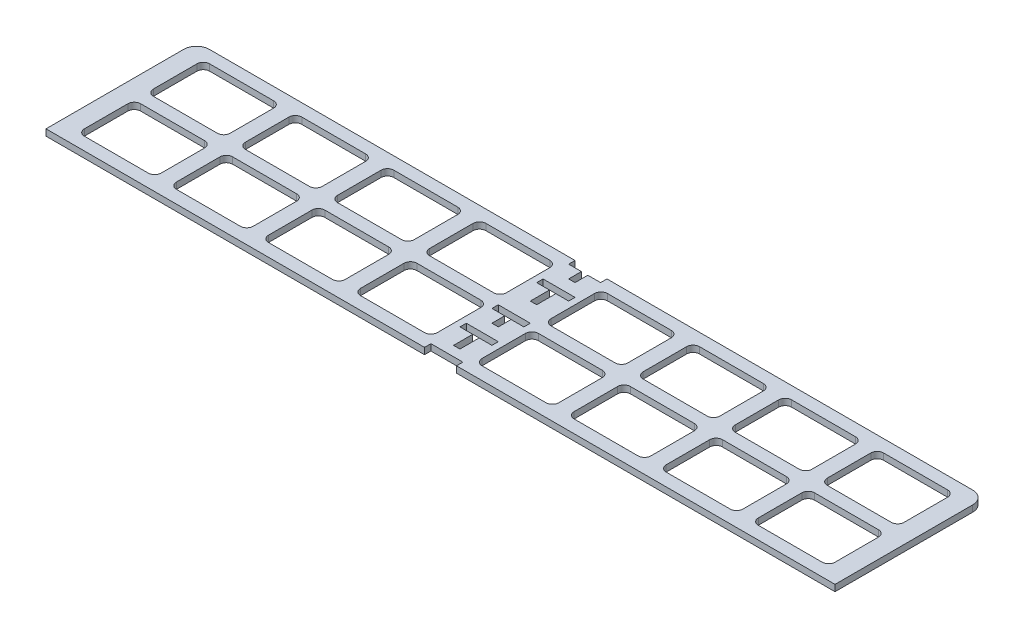
SolidWorks part; units mm, degrees
material "Balsa"
ref_plane "Front Plane" through (0, 0, 0) normal (0, 0, 1) x (1, 0, 0)
ref_plane "Top Plane" through (0, 0, 0) normal (0, 1, 0) x (1, 0, 0)
ref_plane "Right Plane" through (0, 0, 0) normal (1, 0, 0) x (0, 0, -1)
sketch "Sketch1" plane through (0, 0, 0) normal (0, 1, 0) x (1, 0, 0)
  line L0 (0, 0) -> (388.62, 0)
  line L1 (375.92, 149.479) -> (0, 149.479)
  line L3 (388.62, 0) -> (388.62, 136.779)
  line L4 (0, 149.479) -> (0, 130.429)
  line L5 (0, 130.429) -> (-3.175, 130.429)
  line L6 (-3.175, 130.429) -> (-3.175, 111.379)
  line L7 (-3.175, 111.379) -> (0, 111.379)
  line L8 (0, 111.379) -> (0, 92.329)
  line L9 (0, 92.329) -> (-3.175, 92.329)
  line L10 (-3.175, 92.329) -> (-3.175, 73.279)
  line L11 (-3.175, 73.279) -> (0, 73.279)
  line L12 (0, 73.279) -> (0, 54.229)
  line L13 (0, 54.229) -> (-3.175, 54.229)
  line L14 (-3.175, 54.229) -> (-3.175, 35.179)
  line L15 (-3.175, 35.179) -> (0, 35.179)
  line L16 (0, 35.179) -> (0, 16.129)
  line L17 (0, 16.129) -> (-3.175, 16.129)
  line L23 (-3.175, 0) -> (0, 0)
  line L24 (-3.175, 16.129) -> (-3.175, 0)
  arc A0 (375.92, 149.479) -> (388.62, 136.779) centre (375.92, 136.779) cw
  point P7 (388.62, 149.479)
  dimension "D4" = 12.7
  dimension "D22" = 136.779
  dimension "D2" = 388.62
  dimension "D3" = 149.479
  dimension "D5" = 19.05
  dimension "D6" = 19.05
  dimension "D7" = 3.175
  dimension "D8" = 19.05
  dimension "D9" = 19.05
  dimension "D10" = 19.05
  dimension "D11" = 19.05
  dimension "D12" = 19.05
  dimension "D15" = 3.175
  dimension "D16" = 3.175
  dimension "D17" = 3.175
  dimension "D18" = 375.92
  dimension "D19" = 3.175
  dimension "D23" = 3.175
extrude "Boss-Extrude1" add sketch "Sketch1" along normal blind 6.35
sketch "Sketch2" plane through (0, 6.35, 0) normal (0, 1, 0) x (1, 0, 0)
  line L0 (110.49, 19.05) -> (110.49, 62.23)
  line L9 (116.84, 12.7) -> (180.34, 12.7)
  line L82 (186.69, 19.05) -> (186.69, 62.23)
  line L83 (116.84, 68.58) -> (180.34, 68.58)
  line L84 (201.93, 19.05) -> (201.93, 62.23)
  line L85 (208.28, 12.7) -> (271.78, 12.7)
  line L86 (278.13, 19.05) -> (278.13, 62.23)
  line L87 (208.28, 68.58) -> (271.78, 68.58)
  line L88 (293.37, 19.05) -> (293.37, 62.23)
  line L89 (299.72, 12.7) -> (363.22, 12.7)
  line L90 (369.57, 19.05) -> (369.57, 62.23)
  line L91 (25.4, 12.7) -> (88.9, 12.7)
  line L92 (19.05, 19.05) -> (19.05, 62.23)
  line L93 (25.4, 68.58) -> (88.9, 68.58)
  line L94 (95.25, 19.05) -> (95.25, 62.23)
  line L95 (299.72, 68.58) -> (363.22, 68.58)
  line L96 (110.49, 87.63) -> (110.49, 130.81)
  line L97 (116.84, 81.28) -> (180.34, 81.28)
  line L98 (186.69, 87.63) -> (186.69, 130.81)
  line L99 (116.84, 137.16) -> (180.34, 137.16)
  line L100 (201.93, 87.63) -> (201.93, 130.81)
  line L101 (208.28, 81.28) -> (271.78, 81.28)
  line L102 (278.13, 87.63) -> (278.13, 130.81)
  line L103 (208.28, 137.16) -> (271.78, 137.16)
  line L104 (293.37, 87.63) -> (293.37, 130.81)
  line L105 (299.72, 81.28) -> (363.22, 81.28)
  line L106 (369.57, 87.63) -> (369.57, 130.81)
  line L107 (299.72, 137.16) -> (363.22, 137.16)
  line L108 (19.05, 87.63) -> (19.05, 130.81)
  line L109 (25.4, 81.28) -> (88.9, 81.28)
  line L110 (95.25, 87.63) -> (95.25, 130.81)
  line L111 (25.4, 137.16) -> (88.9, 137.16)
  arc A0 (88.9, 12.7) -> (95.25, 19.05) centre (88.9, 19.05) ccw
  arc A1 (25.4, 12.7) -> (19.05, 19.05) centre (25.4, 19.05) cw
  arc A2 (19.05, 62.23) -> (25.4, 68.58) centre (25.4, 62.23) cw
  arc A3 (88.9, 68.58) -> (95.25, 62.23) centre (88.9, 62.23) cw
  arc A4 (110.49, 62.23) -> (116.84, 68.58) centre (116.84, 62.23) cw
  arc A5 (116.84, 12.7) -> (110.49, 19.05) centre (116.84, 19.05) cw
  arc A6 (180.34, 12.7) -> (186.69, 19.05) centre (180.34, 19.05) ccw
  arc A7 (180.34, 68.58) -> (186.69, 62.23) centre (180.34, 62.23) cw
  arc A8 (201.93, 62.23) -> (208.28, 68.58) centre (208.28, 62.23) cw
  arc A9 (208.28, 12.7) -> (201.93, 19.05) centre (208.28, 19.05) cw
  arc A10 (271.78, 12.7) -> (278.13, 19.05) centre (271.78, 19.05) ccw
  arc A11 (271.78, 68.58) -> (278.13, 62.23) centre (271.78, 62.23) cw
  arc A12 (293.37, 62.23) -> (299.72, 68.58) centre (299.72, 62.23) cw
  arc A13 (299.72, 12.7) -> (293.37, 19.05) centre (299.72, 19.05) cw
  arc A14 (363.22, 12.7) -> (369.57, 19.05) centre (363.22, 19.05) ccw
  arc A15 (363.22, 68.58) -> (369.57, 62.23) centre (363.22, 62.23) cw
  arc A16 (110.49, 130.81) -> (116.84, 137.16) centre (116.84, 130.81) cw
  arc A17 (116.84, 81.28) -> (110.49, 87.63) centre (116.84, 87.63) cw
  arc A18 (180.34, 81.28) -> (186.69, 87.63) centre (180.34, 87.63) ccw
  arc A19 (180.34, 137.16) -> (186.69, 130.81) centre (180.34, 130.81) cw
  arc A20 (201.93, 130.81) -> (208.28, 137.16) centre (208.28, 130.81) cw
  arc A21 (208.28, 81.28) -> (201.93, 87.63) centre (208.28, 87.63) cw
  arc A22 (271.78, 81.28) -> (278.13, 87.63) centre (271.78, 87.63) ccw
  arc A23 (271.78, 137.16) -> (278.13, 130.81) centre (271.78, 130.81) cw
  arc A24 (293.37, 130.81) -> (299.72, 137.16) centre (299.72, 130.81) cw
  arc A25 (299.72, 81.28) -> (293.37, 87.63) centre (299.72, 87.63) cw
  arc A26 (363.22, 81.28) -> (369.57, 87.63) centre (363.22, 87.63) ccw
  arc A27 (363.22, 137.16) -> (369.57, 130.81) centre (363.22, 130.81) cw
  arc A28 (19.05, 130.81) -> (25.4, 137.16) centre (25.4, 130.81) cw
  arc A29 (25.4, 81.28) -> (19.05, 87.63) centre (25.4, 87.63) cw
  arc A30 (88.9, 81.28) -> (95.25, 87.63) centre (88.9, 87.63) ccw
  arc A31 (88.9, 137.16) -> (95.25, 130.81) centre (88.9, 130.81) cw
  point P10 (95.25, 12.7)
  point P13 (19.05, 12.7)
  point P16 (19.05, 68.58)
  dimension "D7" = 2
  dimension "D5" = 6.35
  dimension "D2" = 76.2
  dimension "D3" = 12.7
  dimension "D4" = 55.88
  dimension "D8" = 12.7
  dimension "D9" = 19.05
  dimension "D10" = 15.24
  dimension "D11" = 19.05
  dimension "D6" = 4
extrude "Weight Saving Holes" cut sketch "Sketch2" against normal up to surface (6.35 mm away) up to face at (59.4942, 0, -77.067)
mirror "Mirror1" about plane through (-3.175, 6.35, -54.229) normal (1, 0, 0) of "Weight Saving Holes", "Boss-Extrude1"
sketch "Sketch3" plane through (0, 6.35, 0) normal (0, 1, 0) x (1, 0, 0)
  line L8 (-19.05, 143.129) -> (12.7, 143.129)
  line L9 (-19.05, 143.129) -> (-19.05, 149.479)
  line L10 (-19.05, 149.479) -> (12.7, 149.479)
  line L11 (12.7, 143.129) -> (12.7, 149.479)
  line L12 (-19.05, 111.379) -> (12.7, 111.379)
  line L13 (-19.05, 111.379) -> (-19.05, 117.729)
  line L14 (-19.05, 117.729) -> (12.7, 117.729)
  line L15 (12.7, 111.379) -> (12.7, 117.729)
  line L20 (-19.05, 0) -> (12.7, 0)
  line L21 (-19.05, 0) -> (-19.05, 6.35)
  line L22 (-19.05, 6.35) -> (12.7, 6.35)
  line L23 (12.7, 0) -> (12.7, 6.35)
  line L24 (-19.05, 66.929) -> (12.7, 66.929)
  line L25 (-19.05, 66.929) -> (-19.05, 73.279)
  line L26 (-19.05, 73.279) -> (12.7, 73.279)
  line L27 (12.7, 66.929) -> (12.7, 73.279)
  line L28 (-19.05, 35.179) -> (12.7, 35.179)
  line L29 (-19.05, 35.179) -> (-19.05, 41.529)
  line L30 (-19.05, 41.529) -> (12.7, 41.529)
  line L31 (12.7, 35.179) -> (12.7, 41.529)
  line L32 (0, 130.429) -> (-6.35, 130.429) construction
  line L33 (375.92, 149.479) -> (0, 149.479) construction
  line L35 (-6.35, 111.379) -> (0, 111.379) construction
  line L36 (-6.35, 73.279) -> (0, 73.279) construction
  line L37 (-6.35, 35.179) -> (0, 35.179) construction
  line L39 (-394.97, 0) -> (388.62, 0) construction
  point P0 (-3.175, 130.429)
  point P1 (-3.175, 149.479)
  point P4 (-3.175, 117.729)
  point P5 (-3.175, 73.279)
  point P6 (-3.175, 41.529)
  point P7 (-3.175, 36.576)
  point P24 (-3.175, 6.35)
  dimension "D5" = 31.75
  dimension "D6" = 6.35
  dimension "D7" = 31.75
  dimension "D8" = 6.35
  dimension "D11" = 31.75
  dimension "D12" = 6.35
  dimension "D13" = 31.75
  dimension "D14" = 6.35
  dimension "D15" = 31.75
  dimension "D16" = 6.35
extrude "Boom Bracket Attachment Slots" cut sketch "Sketch3" against normal through all
equation "\"D7@Sketch3\"=\"D5@Sketch3\""
equation "\"D13@Sketch3\"=\"D5@Sketch3\""
equation "\"D15@Sketch3\"=\"D5@Sketch3\""
equation "\"D11@Sketch3\"=\"D5@Sketch3\""
